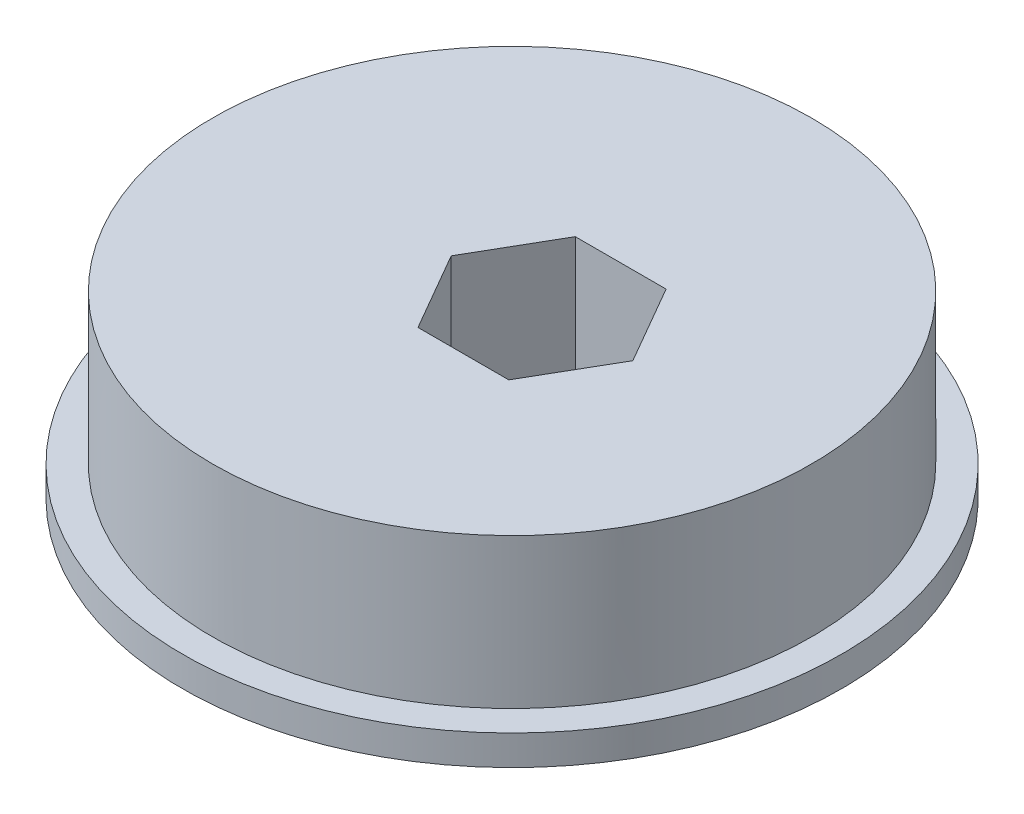
SolidWorks part; units mm, degrees
ref_plane "Front Plane" through (0, 0, 0) normal (0, 0, 1) x (1, 0, 0)
ref_plane "Top Plane" through (0, 0, 0) normal (0, 1, 0) x (1, 0, 0)
ref_plane "Right Plane" through (0, 0, 0) normal (1, 0, 0) x (0, 0, -1)
sketch "Sketch1" plane through (0, 0, 0) normal (0, 1, 0) x (1, 0, 0)
  line L0 (0, 0) -> (-1, 0) construction
  circle A1 centre (-1, 0) radius 10
  point P12 (0, 0)
  dimension "D3" = 20
  dimension "D2" = 1
extrude "Boss-Extrude1" add sketch "Sketch1" along normal blind 6
sketch "Sketch2" plane through (0, 0, 0) normal (0, -1, 0) x (1, 0, 0)
  line L0 (-12.8187, 0) -> (7.6603, 0) construction
  circle A0 centre (-1, 0) radius 11
  dimension "D2" = 22
  dimension "D1" = 1
extrude "Boss-Extrude2" add sketch "Sketch2" against normal blind 1
sketch "Sketch4" plane through (0, 6, 0) normal (0, 1, 0) x (1, 0, 0)
  line L0 (0, 8.8969) -> (0, -8.7328) construction
  line L2 (3.0311, 0) -> (1.5155, 2.625)
  line L3 (1.5155, 2.625) -> (-1.5155, 2.625)
  line L4 (-1.5155, 2.625) -> (-3.0311, 0)
  line L5 (-3.0311, 0) -> (-1.5155, -2.625)
  line L6 (-1.5155, -2.625) -> (1.5155, -2.625)
  line L7 (1.5155, -2.625) -> (3.0311, 0)
  circle A0 centre (0, 0) radius 5.5 construction
  circle A3 centre (0, 0) radius 2 construction
  circle A4 centre (0, 0) radius 2.625 construction
  dimension "D1" = 11
  dimension "D2" = 4
  dimension "D3" = 5.25
extrude "Cut-Extrude1" cut sketch "Sketch4" against normal through all
